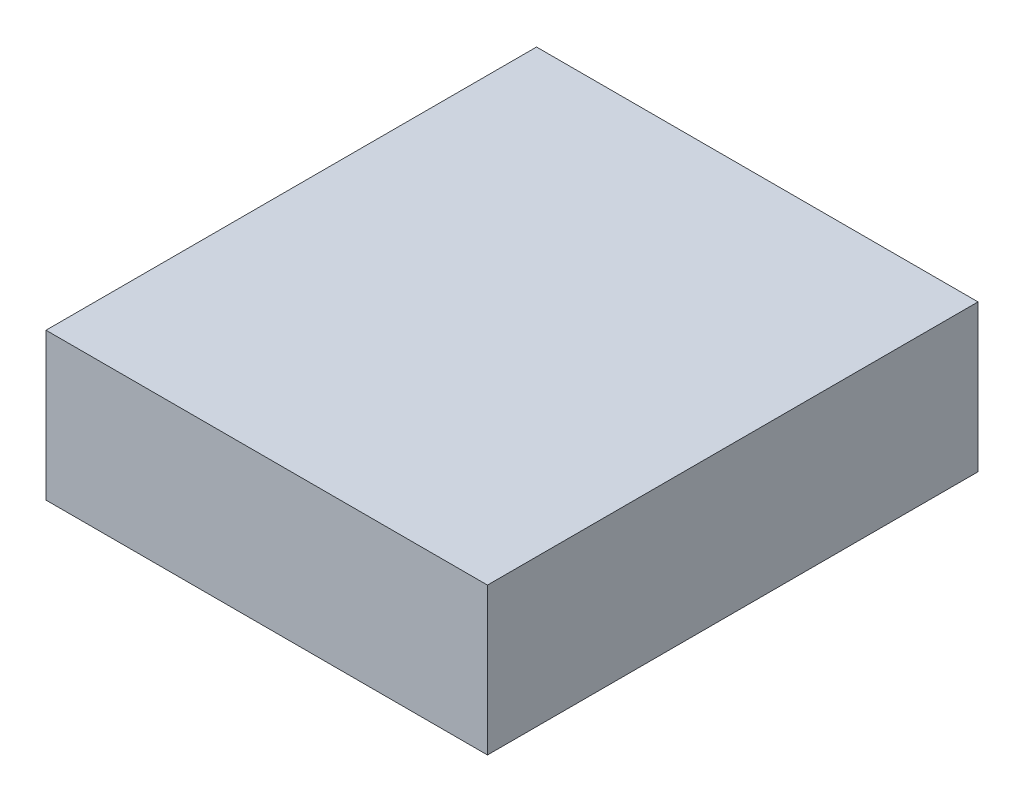
SolidWorks part; units mm, degrees
material "Aço 4140"
ref_plane "Plano frontal" through (0, 0, 0) normal (0, 0, 1) x (1, 0, 0)
ref_plane "Plano superior" through (0, 0, 0) normal (0, 1, 0) x (1, 0, 0)
ref_plane "Plano direito" through (0, 0, 0) normal (1, 0, 0) x (0, 0, -1)
sketch "Esboço1" plane through (0, 0, 0) normal (1, 0, 0) x (0, 0, -1)
  line L1 (-50, -15) -> (50, -15)
  line L2 (-50, -15) -> (-50, 15)
  line L3 (-50, 15) -> (50, 15)
  line L4 (50, -15) -> (50, 15)
  line L5 (-50, -15) -> (50, 15) construction
  line L6 (-50, 15) -> (50, -15) construction
  point P0 (0, 0)
  dimension "D1" = 100
  dimension "D2" = 30
extrude "Ressalto-extrusão1" add sketch "Esboço1" along normal blind 90
